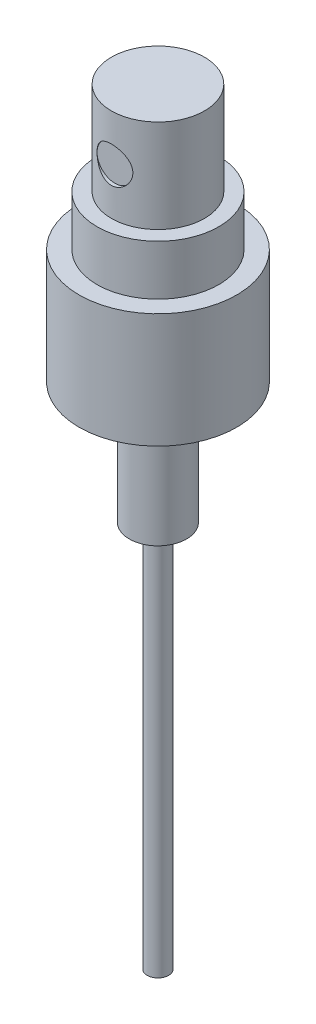
SolidWorks part; units mm, degrees
material "ПВХ Жесткий"
ref_plane "Спереди" through (0, 0, 0) normal (0, 0, 1) x (1, 0, 0)
ref_plane "Сверху" through (0, 0, 0) normal (0, 1, 0) x (1, 0, 0)
ref_plane "Справа" through (0, 0, 0) normal (1, 0, 0) x (0, 0, -1)
sketch "Эскиз1" plane through (0, 0, 0) normal (0, 1, 0) x (1, 0, 0)
  circle A0 centre (0, 0) radius 11
  dimension "D1" = 22
extrude "Бобышка-Вытянуть1" add sketch "Эскиз1" along normal blind 16
sketch "Эскиз2" plane through (0, 0, 0) normal (0, -1, 0) x (1, 0, 0)
  circle A0 centre (0, 0) radius 10
  dimension "D1" = 20
extrude "Вырез-Вытянуть1" cut sketch "Эскиз2" against normal blind 14
thread "Резьба2" pitch 3.175 method extrude profile "Профиль резьбы5" start angle 0, offset 0, length 7, pitch 3.175, diameter 20
ref_plane "Плоскость5" through (-10, 14, 0) normal (0, 0, -1) x (1, 0, 0)
sketch "Профиль резьбы5" plane through (-10, 14, 0) normal (0, 0, -1) x (1, 0, 0)
  line L0 (0, 0) -> (0, 3.175) construction
  line L1 (0, 0) -> (0, 2.6624)
  line L2 (0.254, 2.6624) -> (1.0668, 2.6624) construction
  line L3 (1.0668, 2.048) -> (1.0668, 1.6981)
  line L4 (0.8569, 2.2981) -> (0.2099, 2.4122)
  line L5 (0.8436, 1.1592) -> (0.2232, 0.5388)
  line L6 (0.762, 0) -> (1.0668, 0) construction
  arc A0 (0.2099, 2.4122) -> (0, 2.6624) centre (0.254, 2.6624) cw
  arc A1 (0.2232, 0.5388) -> (0, 0) centre (0.762, 0) ccw
  arc A2 (1.0668, 1.6981) -> (0.8436, 1.1592) centre (0.3048, 1.6981) cw
  arc A3 (1.0668, 2.048) -> (0.8569, 2.2981) centre (0.8128, 2.048) ccw
  point P10 (1.0668, 2.2611)
  point P17 (1.0668, 1.3824)
  point P18 (0, 2.4492)
  point P19 (0, 0.3156)
  point P20 (0, 0)
  dimension "RootFillet1" = 0.254
  dimension "RootFillet2" = 0.762
  dimension "CrestFillet2" = 0.762
  dimension "CrestFillet1" = 0.254
  dimension "Pitch" = 3.175
  dimension "Angle1" = 10
  dimension "Angle2" = 45
  dimension "a" = 2.1336
  dimension "b" = 1.0668
  dimension "c" = 0.8787
sketch "Эскиз18" plane through (0, 16, 0) normal (0, 1, 0) x (1, 0, 0)
  circle A0 centre (0, 0) radius 8.5
  dimension "D1" = 17
extrude "Бобышка-Вытянуть3" add sketch "Эскиз18" along normal blind 7
sketch "Эскиз19" plane through (0, 23, 0) normal (0, 1, 0) x (1, 0, 0)
  circle A0 centre (0, 0) radius 6.5
  dimension "D1" = 13
extrude "Бобышка-Вытянуть4" add sketch "Эскиз19" along normal blind 13
sketch "Эскиз20" plane through (0, 0, 0) normal (0, 0, 1) x (1, 0, 0)
  line L0 (0, 0) -> (0, 23) construction
  line L1 (8.5, 23) -> (-8.5, 23) construction
  line L2 (0, 23) -> (0, 36) construction
  line L3 (6.5, 36) -> (-6.5, 36) construction
  circle A0 centre (0, 29.5) radius 2.5
  dimension "D1" = 5
extrude "Вырез-Вытянуть2" cut sketch "Эскиз20" against normal blind 7 from offset 13
sketch "Эскиз21" plane through (0, 14, 0) normal (0, -1, 0) x (1, 0, 0)
  circle A0 centre (0, 0) radius 4
  dimension "D1" = 8
extrude "Бобышка-Вытянуть5" add sketch "Эскиз21" along normal blind 31
sketch "Эскиз22" plane through (0, -17, 0) normal (0, -1, 0) x (1, 0, 0)
  circle A0 centre (0, 0) radius 1.5
  dimension "D1" = 3
extrude "Бобышка-Вытянуть6" add sketch "Эскиз22" along normal blind 54
